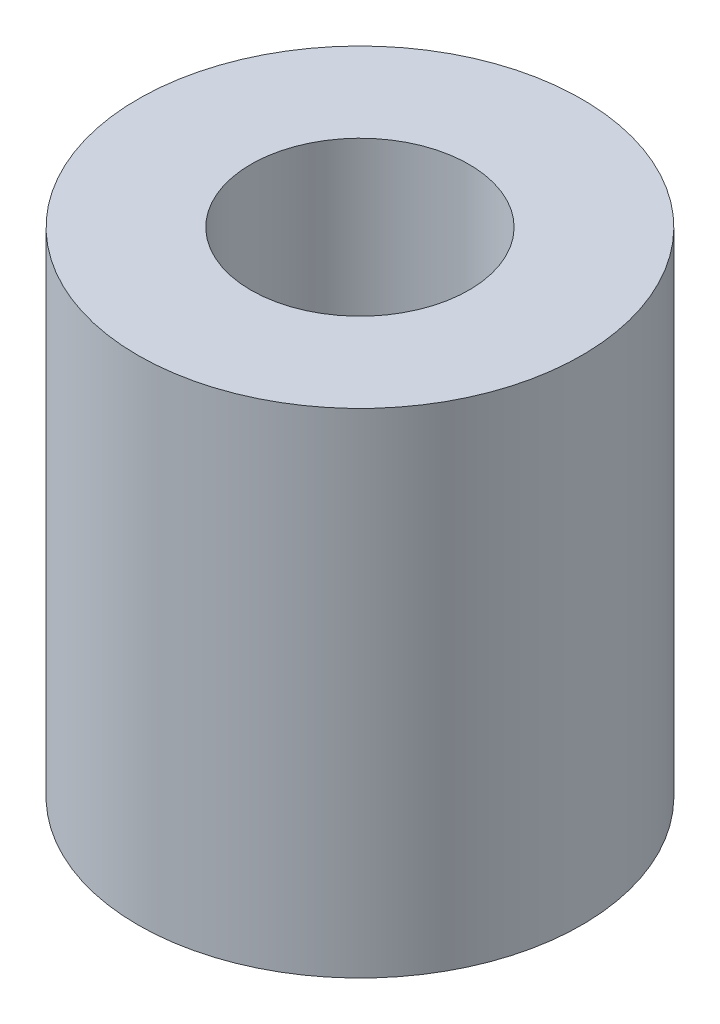
SolidWorks part; units mm, degrees
ref_plane "Front Plane" through (0, 0, 0) normal (0, 0, 1) x (1, 0, 0)
ref_plane "Top Plane" through (0, 0, 0) normal (0, 1, 0) x (1, 0, 0)
ref_plane "Right Plane" through (0, 0, 0) normal (1, 0, 0) x (0, 0, -1)
sketch "Sketch1" plane through (0, 0, 0) normal (0, 1, 0) x (1, 0, 0)
  circle A0 centre (0, 0) radius 10
  dimension "D1" = 20
extrude "Boss-Extrude1" add sketch "Sketch1" along normal blind 22.225
sketch "Sketch2" plane through (0, 22.225, 0) normal (0, 1, 0) x (1, 0, 0)
  circle A0 centre (0, 0) radius 4.9125
  point P0 (0, 0)
  dimension "D1" = 9.825
extrude "Cut-Extrude1" cut sketch "Sketch2" against normal through all contours A0
